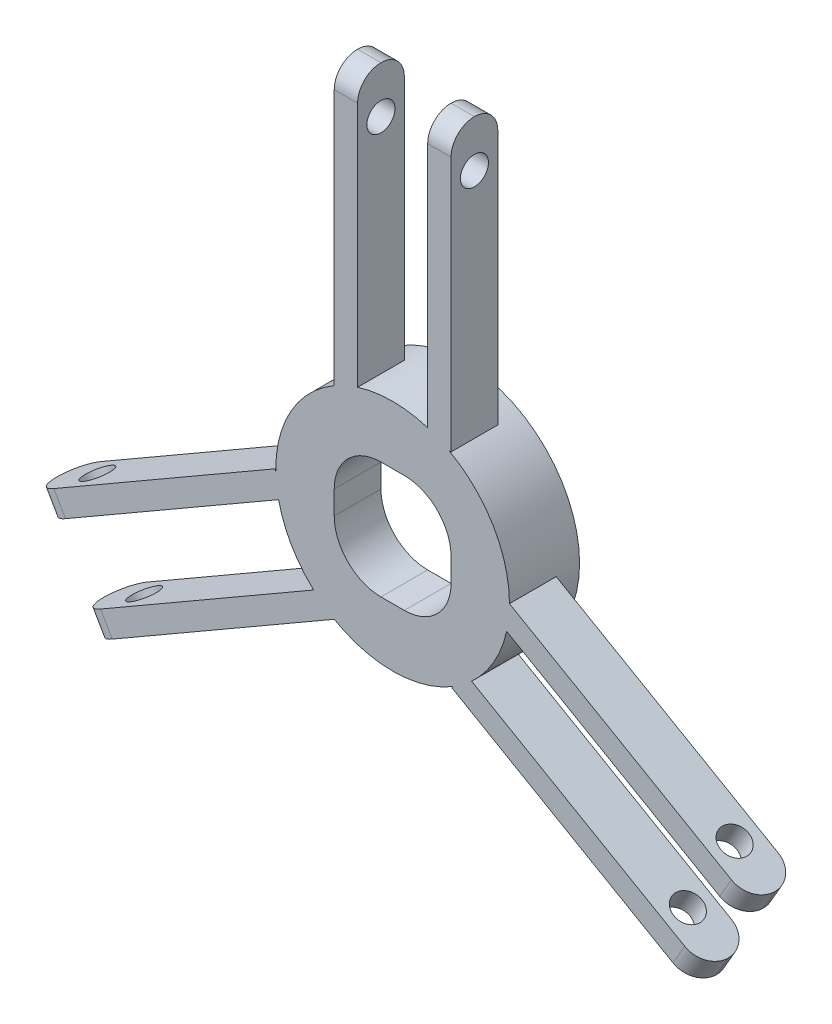
SolidWorks part; units mm, degrees
material "7075-T6 (SN)"
ref_plane "Front Plane" through (0, 0, 0) normal (0, 0, 1) x (1, 0, 0)
ref_plane "Top Plane" through (0, 0, 0) normal (0, 1, 0) x (1, 0, 0)
ref_plane "Right Plane" through (0, 0, 0) normal (1, 0, 0) x (0, 0, -1)
sketch "Sketch1" plane through (0, 0, 0) normal (0, 0, 1) x (1, 0, 0)
  line L1 (-2.5, 12.5) -> (2.5, 12.5)
  line L2 (-12.5, 2.5) -> (-12.5, -2.5)
  line L3 (-2.5, -12.5) -> (2.5, -12.5)
  line L4 (12.5, 2.5) -> (12.5, -2.5)
  line L5 (-12.5, 12.5) -> (12.5, -12.5) construction
  line L6 (-12.5, -12.5) -> (12.5, 12.5) construction
  circle A0 centre (0, 0) radius 25
  arc A1 (-2.5, 12.5) -> (-12.5, 2.5) centre (-2.5, 2.5) ccw
  arc A2 (-12.5, -2.5) -> (-2.5, -12.5) centre (-2.5, -2.5) ccw
  arc A3 (2.5, -12.5) -> (12.5, -2.5) centre (2.5, -2.5) ccw
  arc A4 (2.5, 12.5) -> (12.5, 2.5) centre (2.5, 2.5) cw
  dimension "D1" = 50
  dimension "D4" = 10
  dimension "D2" = 25
  dimension "D3" = 25
extrude "Boss-Extrude1" add sketch "Sketch1" along normal blind 10
sketch "Sketch2" plane through (0, 0, 10) normal (0, 0, 1) x (1, 0, 0)
  line L0 (0, 0) -> (0, 81.5)
  line L1 (-12.5, 81.5) -> (12.5, 81.5) construction
  line L3 (-12.5, 81.5) -> (-7.5, 81.5)
  line L4 (-12.5, 81.5) -> (-12.5, 21.5943)
  line L5 (-12.5, 21.5943) -> (-7.5, 21.5943)
  line L6 (-7.5, 81.5) -> (-7.5, 21.5943)
  line L7 (12.5, 81.5) -> (7.5, 81.5)
  line L8 (12.5, 81.5) -> (12.5, 21.8665)
  line L9 (12.5, 21.8665) -> (7.5, 21.8665)
  line L10 (7.5, 81.5) -> (7.5, 21.8665)
  point P6 (0, 81.5)
  circle M8 centre (0, 0) radius 25
  dimension "D1" = 81.5
  dimension "D2" = 25
  dimension "D3" = 5
  dimension "D4" = 5
extrude "Boss-Extrude3" add sketch "Sketch2" against normal blind 10 contours L6 L3 L4 M8 | L8 L7 L10 L9 region at (-10.0156, 52.1759, 10)
sketch "Sketch3" plane through (12.5, 0, 0) normal (1, 0, 0) x (0, 0, -1)
  line L0 (-5, 81.5) -> (-5, 71.5) construction
  line L1 (0, 81.5) -> (-10, 81.5) construction
  circle A0 centre (-5, 71.5) radius 3
  dimension "D2" = 6
  dimension "D1" = 10
extrude "Cut-Extrude1" cut sketch "Sketch3" against normal blind 29
fillet "Fillet1" radius 5 4 edges at (-10, 81.5, 10) (-10, 81.5, 0) (10, 81.5, 0) (10, 81.5, 10)
pattern_circular "CirPattern1" count 3 over 360 about axis through (0, 0, 10) along (0, 0, 1) of "Boss-Extrude3", "Cut-Extrude1", "Fillet1"
sketch "Sketch5" plane through (0, 0, 0) normal (0, 0, -1) x (-1, 0, 0)
  circle A0 centre (0, 0) radius 22.5
  circle A1 centre (0, 0) radius 25
  dimension "D1" = 50
  dimension "D2" = 45
extrude "Boss-Extrude5" add sketch "Sketch5" along normal blind 5
